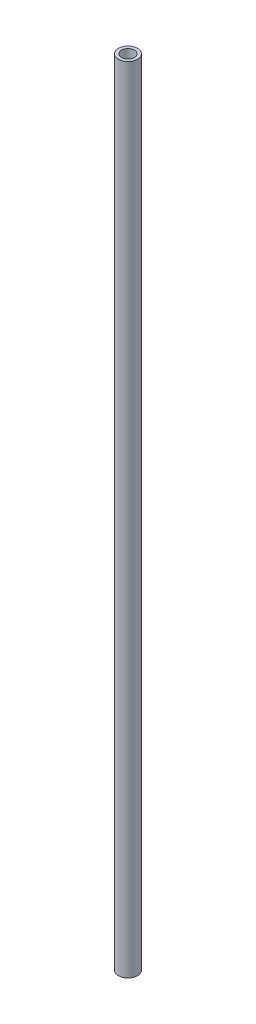
SolidWorks part; units mm, degrees
ref_plane "Front Plane" through (0, 0, 0) normal (0, 0, 1) x (1, 0, 0)
ref_plane "Top Plane" through (0, 0, 0) normal (0, 1, 0) x (1, 0, 0)
ref_plane "Right Plane" through (0, 0, 0) normal (1, 0, 0) x (0, 0, -1)
sketch "Sketch1" plane through (0, 0, 0) normal (0, 1, 0) x (1, 0, 0)
  circle A0 centre (0, 0) radius 4.8895
  circle A1 centre (0, 0) radius 3.302
  dimension "D2" = 9.779
  dimension "D1" = 1.5875
extrude "Boss-Extrude1" add sketch "Sketch1" along normal blind 406.4
equation "\"Socket Depth\"= 1.5in'Depth of Sockets in part"
equation "\"Roof Angle\"= 15deg'Angle of spoke to roof"
equation "\"Spoke Diameter\"= .385in'Diameter of spoke"
equation "\"Part Thickness\"= .125in'Thickness of injection-molded walls"
equation "\"Spoke Length\"= 8in'Length of spokes"
equation "\"D2@Sketch1\"= \"Spoke Diameter\""
equation "\"D1@Boss-Extrude1\"=\"Center Spoke\""
equation "\"Spoke Length2\"= 12in'length of spokes"
equation "\"Center Spoke\"= 16in' lenth of center spokess"
